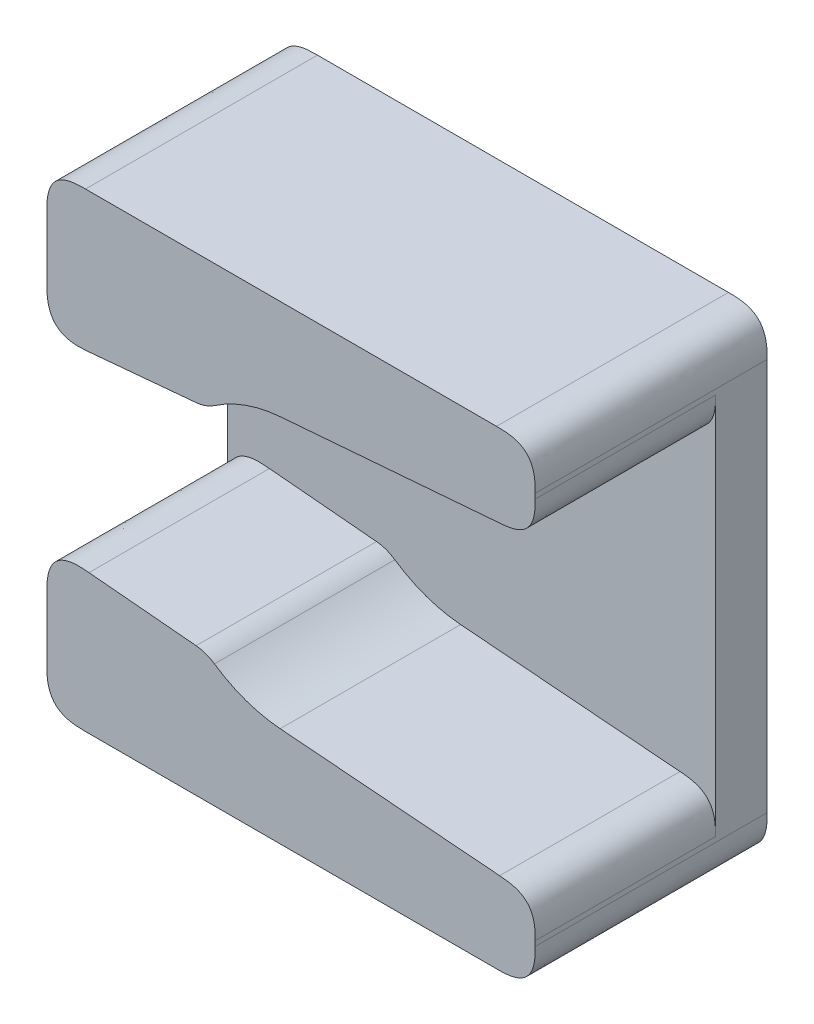
SolidWorks part; units mm, degrees
ref_plane "Front Plane" through (0, 0, 0) normal (0, 0, 1) x (1, 0, 0)
ref_plane "Top Plane" through (0, 0, 0) normal (0, 1, 0) x (1, 0, 0)
ref_plane "Right Plane" through (0, 0, 0) normal (1, 0, 0) x (0, 0, -1)
sketch "Sketch2" plane through (0, 0, 0) normal (0, 0, 1) x (1, 0, 0)
  line L1 (-351.497, 417.9288) -> (-256.7458, 417.9288)
  line L2 (-351.497, 417.9288) -> (-351.497, 326.7649)
  line L3 (-351.497, 326.7649) -> (-256.7458, 326.7649)
  line L4 (-256.7458, 417.9288) -> (-256.7458, 326.7649)
  line L5 (-351.497, 417.9288) -> (-256.7458, 326.7649) construction
  line L6 (-351.497, 326.7649) -> (-256.7458, 417.9288) construction
  point P0 (-304.1214, 372.3469)
extrude "Boss-Extrude1" add sketch "Sketch2" along normal blind 45
sketch "Sketch5" plane through (0, 0, 45) normal (0, 0, 1) x (1, 0, 0)
  line L0 (-306.2215, 398.5629) -> (-238.9312, 403.9533)
  line L1 (-367.8699, 372.3469) -> (-233.8008, 372.3469) construction
  line L2 (-306.2215, 346.1309) -> (-238.9312, 340.7405)
  line L3 (-306.1038, 394.2574) -> (-371.3298, 388.3558)
  line L4 (-306.1038, 350.4364) -> (-371.3298, 356.338)
  line L5 (-371.3298, 388.3558) -> (-371.3298, 356.338)
  line L6 (-238.9312, 403.9533) -> (-238.9312, 340.7405)
  circle A0 centre (-304.1214, 372.3469) radius 26.3
  circle A1 centre (-304.1214, 372.3469) radius 22
  dimension "D1" = 52.6
  dimension "D2" = 4.58
  dimension "D4" = 44
  dimension "D3" = 2.1001
  dimension "D5" = 10.34
extrude "Cut-Extrude3" cut sketch "Sketch5" against normal blind 35
fillet "Fillet2" radius 7.5 8 edges at (-351.497, 326.7649, 22.5) (-351.497, 354.5435, 27.5) (-351.497, 390.1502, 27.5) (-351.497, 417.9288, 22.5) (-256.7458, 417.9288, 22.5) (-256.7458, 326.7649, 22.5) (-256.7458, 342.1675, 27.5) (-256.7458, 402.5262, 27.5) curvature continuous yes
fillet "Fillet3" radius 7.5 2 edges at (-320.4566, 351.735, 27.5) (-320.4566, 392.9587, 27.5)
